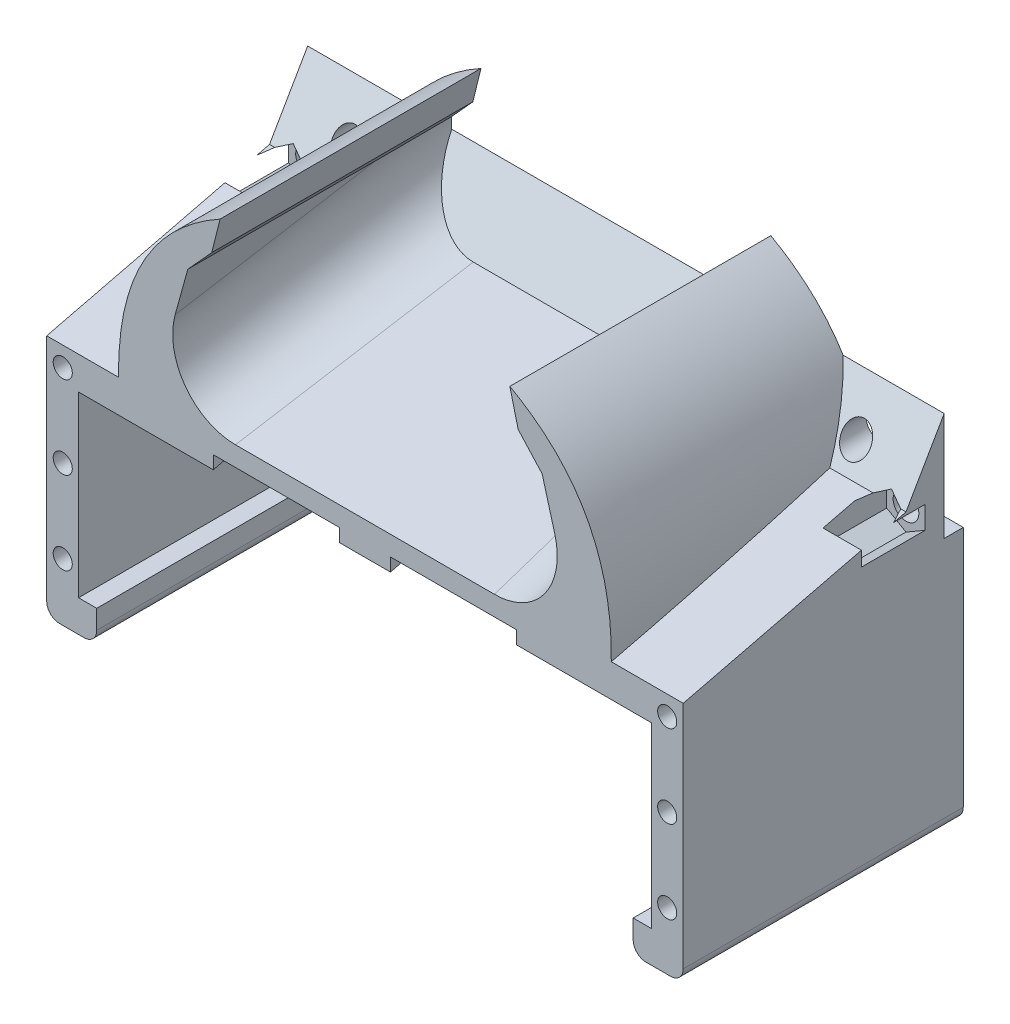
SolidWorks part; units mm, degrees
ref_plane "Alzado" through (0, 0, 0) normal (0, 0, 1) x (1, 0, 0)
ref_plane "Planta" through (0, 0, 0) normal (0, 1, 0) x (1, 0, 0)
ref_plane "Vista lateral" through (0, 0, 0) normal (1, 0, 0) x (0, 0, -1)
sketch "Croquis1" plane through (0, 0, 0) normal (0, 0, 1) x (1, 0, 0)
  line L0 (-50, -27.25) -> (-50, -29.8252)
  line L1 (-50, 27.25) -> (50, 27.25)
  line L2 (-50, 27.25) -> (-50, -27.25)
  line L4 (50, 27.25) -> (50, -27.25)
  line L5 (-50, 27.25) -> (50, -27.25) construction
  line L6 (-50, -27.25) -> (50, 27.25) construction
  line L8 (50, -29.8252) -> (50, -27.25)
  line L9 (50, -29.8252) -> (-50, -29.8252)
  point P0 (0, 0)
  dimension "D1" = 100
  dimension "D2" = 54.5
extrude "Saliente-Extruir1" add sketch "Croquis1" along normal blind 46
sketch "Croquis3" plane through (-50, 0, 0) normal (-1, 0, 0) x (0, 0, 1)
  line L0 (5, 27.25) -> (11, 16.8577)
  line L1 (46, 27.25) -> (0, 27.25) construction
  line L2 (5, 27.25) -> (5, 10.25)
  line L3 (0, 35.6144) -> (0, 11.6144) construction
  line L4 (5, 10.25) -> (-12.1741, 10.25)
  line L5 (-12.1741, 10.25) -> (-12.1741, 43.3906)
  line L6 (5, 27.25) -> (0.1443, 35.6603)
  line L7 (-12.1741, 43.3906) -> (41, 43.3906)
  line L9 (11, 16.8577) -> (46, 8.3186)
  line L10 (46, 27.25) -> (46, -29.8252) construction
  line M5 (0, 27.25) -> (0, -29.8252)
  line M7 (46, -29.8252) -> (46, 27.25)
  line M8 (46, 27.25) -> (0, 27.25)
  dimension "D2" = 17
  dimension "D1" = 5
  dimension "D3" = 12
  dimension "D4" = 30
extrude "Cortar-Extruir1" cut sketch "Croquis3" against normal blind 107 contours L0 M7 M8 | L7 L5 L4 M5 M8 region at (-50, 19.9452, 28.9845) region at (-50, 18.75, 2.5)
shell "Vaciado1" thickness 5 removed face at (0, -10.7533, 46)
sketch "Croquis5" plane through (0, 0, 0) normal (0, 0, -1) x (-1, 0, 0)
  line L0 (-44.969, -22.9415) -> (-44.969, -34.966)
  line L1 (-44.969, 22.9415) -> (44.969, 22.9415)
  line L2 (-44.969, 22.9415) -> (-44.969, -22.9415)
  line L4 (44.969, 22.9415) -> (44.969, -22.9415)
  line L5 (-44.969, 22.9415) -> (44.969, -22.9415) construction
  line L6 (-44.969, -22.9415) -> (44.969, 22.9415) construction
  line L7 (-44.969, -34.966) -> (44.969, -34.966)
  line L8 (44.969, -34.966) -> (44.969, -22.9415)
  point P0 (0, 0)
extrude "Cortar-Extruir3" cut sketch "Croquis5" against normal blind 5 contours L7 L8 L0 | L4 L1 L2 | L8 L0 region at (0, -6.0122, 0)
sketch "Croquis7" plane through (0, 0, 0) normal (0, 0, -1) x (-1, 0, 0)
  line L1 (-14.0425, 6.8203) -> (14.0425, 6.8203)
  line L2 (-14.0425, 6.8203) -> (-14.0425, -6.8203)
  line L3 (-14.0425, -6.8203) -> (14.0425, -6.8203)
  line L4 (14.0425, 6.8203) -> (14.0425, -6.8203)
  line L5 (-14.0425, 6.8203) -> (14.0425, -6.8203) construction
  line L6 (-14.0425, -6.8203) -> (14.0425, 6.8203) construction
  point P0 (0, 0)
extrude "Cortar-Extruir5" cut sketch "Croquis7" against normal blind 2 rebuild error yes
sketch "Croquis8" plane through (0, 0, 2) normal (0, 0, -1) x (-1, 0, 0)
  line L5 (-44.969, -42.8534) -> (44.969, -42.8534) construction
  line L11 (-42.1434, -13.3473) -> (42.1434, -13.3473)
  line L12 (-42.1434, -13.3473) -> (-42.1434, -72.3596)
  line L13 (-42.1434, -72.3596) -> (42.1434, -72.3596)
  line L14 (42.1434, -13.3473) -> (42.1434, -72.3596)
  line L15 (-42.1434, -13.3473) -> (42.1434, -72.3596) construction
  line L16 (-42.1434, -72.3596) -> (42.1434, -13.3473) construction
  point P0 (0, -42.8534)
  point P3 (0, -42.8534)
extrude "Cortar-Extruir6" cut sketch "Croquis8" against normal blind 50
sketch "Croquis9" plane through (0, 0, 5) normal (0, 0, -1) x (-1, 0, 0)
  line L0 (-44.969, 13.7411) -> (44.969, 13.7411)
  line L1 (44.969, 13.7411) -> (44.969, 5.25)
  line L2 (44.969, 5.25) -> (-44.969, 5.25)
  line L3 (-44.969, -29.8252) -> (-44.969, 10.25) construction
  line L4 (-44.969, 10.25) -> (-44.969, 5.25) construction
  line L5 (-44.969, 5.25) -> (-44.969, 13.7411)
extrude "Cortar-Extruir7" cut sketch "Croquis9" against normal blind 10
fillet "Redondeo1" radius 2 2 edges at (42.1434, -29.8252, 25.5) (-50, -29.8252, 23)
fillet "Redondeo2" radius 2 1 edges at (50, -29.8252, 23)
fillet "Redondeo3" radius 2 1 edges at (-42.1434, -29.8252, 25.5)
sketch "Croquis10" plane through (0, 13.5861, 3.3147) normal (0, -0.9715, -0.237) x (1, 0, 0)
  line L0 (23.8272, 1.7967) -> (23.8272, 43.9374)
  line L2 (45, 43.9374) -> (-45, 43.9374) construction
  line L3 (23.8272, 43.9374) -> (4, 43.9374)
  line L4 (4, 43.9374) -> (4, 1.7967)
  line L5 (4, 1.7967) -> (23.8272, 1.7967)
  line L6 (0, 0) -> (0, -11.1234) construction
  line L7 (-4, 1.7967) -> (-23.8272, 1.7967)
  line L8 (-4, 43.9374) -> (-4, 1.7967)
  line L9 (-23.8272, 43.9374) -> (-4, 43.9374)
  line L10 (-23.8272, 1.7967) -> (-23.8272, 43.9374)
  dimension "D1" = 4
extrude "Cortar-Extruir8" cut sketch "Croquis10" against normal blind 2
sketch "Croquis11" plane through (0, 0, 0) normal (0, 0, -1) x (-1, 0, 0)
  circle A0 centre (-47, 14.6144) radius 2.0175
  circle A1 centre (47, 14.6144) radius 1.8911
extrude "Cortar-Extruir9" cut sketch "Croquis11" against normal blind 9
sketch "Croquis12" plane through (0, 0, 0) normal (0, 0, -1) x (-1, 0, 0)
  circle A0 centre (40, 20.6144) radius 2.25
  circle A1 centre (-40, 20.6144) radius 2.25
extrude "Cortar-Extruir10" cut sketch "Croquis12" against normal blind 33
sketch "Croquis13" plane through (0, 0, 5) normal (0, 0, -1) x (-1, 0, 0)
  line L0 (0, 0) -> (0, -9.6191) construction
  line L7 (-14.0425, -6.8203) -> (14.0425, 6.8203) construction
  circle A0 centre (47, 14.6144) radius 2.075
  circle A1 centre (-47, 14.6144) radius 2.075
  dimension "D1" = 4.15
extrude "Cortar-Extruir11" cut sketch "Croquis13" against normal blind 7 from offset 3 offset against normal yes
sketch "Croquis14" plane through (0, 0, 5) normal (0, 0, -1) x (-1, 0, 0)
  line L0 (0, 0) -> (0, -3.5033) construction
  circle A1 centre (-47, 14.6144) radius 2.5
  circle A2 centre (47, 14.6144) radius 2.5
  dimension "D1" = 5
extrude "Cortar-Extruir12" cut sketch "Croquis14" along normal blind 20 and the other way blind 1 from offset 10 rebuild error yes offset against normal yes
sketch "Croquis15" plane through (0, 0, 15) normal (0, 0, -1) x (-1, 0, 0)
  line L0 (-44.969, 10.7351) -> (-37.0015, 10.7351)
  line L1 (-44.969, 10.7351) -> (-23.8272, 10.7351) construction
  line L2 (-37.0015, 10.7351) -> (-37.0015, 13.7411)
  line L3 (44.969, 13.7411) -> (-44.969, 13.7411) construction
  line L4 (-44.969, 10.7351) -> (-44.969, 13.7411)
  line L5 (-44.969, 13.7411) -> (-37.0015, 13.7411)
  line L6 (0, 0) -> (0, 2.3673)
  line L7 (44.969, 13.7411) -> (37.0015, 13.7411)
  line L8 (44.969, 10.7351) -> (44.969, 13.7411)
  line L9 (37.0015, 10.7351) -> (37.0015, 13.7411)
  line L10 (44.969, 10.7351) -> (37.0015, 10.7351)
  line M3 (-44.969, 13.7411) -> (-44.969, 10.7351)
  line M4 (-44.969, 10.7351) -> (-23.8272, 10.7351)
  line M12 (23.8272, 10.7351) -> (44.969, 10.7351)
  line M13 (44.969, 10.7351) -> (44.969, 13.7411)
  line M15 (44.969, 13.7411) -> (-44.969, 13.7411)
extrude "Saliente-Extruir2" add sketch "Croquis15" along normal blind 10 contours L2 M4 M15 M3 | L9 M12 M13 M15 region at (40.9852, 12.2381, 15) region at (-40.9852, 12.2381, 15)
sketch "Croquis16" plane through (0, 0, 0) normal (0, 0, -1) x (-1, 0, 0)
  line L0 (-44.969, 10.25) -> (-50, 10.25) construction
  line L1 (0, 0) -> (0, -14.3372) construction
  circle A0 centre (-47.4845, 5.25) radius 1.5
  circle A1 centre (-47.4845, -20.75) radius 1.5
  circle A2 centre (-47.4845, -7.75) radius 1.5
  circle A3 centre (47.4845, -7.75) radius 1.5
  circle A4 centre (47.4845, -20.75) radius 1.5
  circle A5 centre (47.4845, 5.25) radius 1.5
  point P8 (-47.4845, 10.25)
  dimension "D1" = 3
  dimension "D2" = 3
  dimension "D3" = 3
  dimension "D4" = 13
  dimension "D5" = 13
  dimension "D6" = 5
extrude "Cortar-Extruir13" cut sketch "Croquis16" against normal blind 73
sketch "Croquis17" plane through (0, 0, 0) normal (0, 0, -1) x (-1, 0, 0)
  line L1 (-62.0795, 36.9151) -> (62.0795, 36.9151)
  line L2 (-62.0795, 36.9151) -> (-62.0795, -36.9151)
  line L3 (-62.0795, -36.9151) -> (62.0795, -36.9151)
  line L4 (62.0795, 36.9151) -> (62.0795, -36.9151)
  line L5 (-62.0795, 36.9151) -> (62.0795, -36.9151) construction
  line L6 (-62.0795, -36.9151) -> (62.0795, 36.9151) construction
  point P0 (0, 0)
extrude "Cortar-Extruir14" cut sketch "Croquis17" against normal blind 2
sketch "Croquis18" plane through (0, 0, 46) normal (0, 0, 1) x (1, 0, 0)
  line L0 (-50, 8.3186) -> (50, 8.3186)
  line L1 (50, 8.3186) -> (50, 5.461)
  line L2 (50, -27.8252) -> (50, 8.3186) construction
  line L3 (50, 5.461) -> (-50, 5.461)
  line L4 (-50, 8.3186) -> (-50, -27.8252) construction
  line L5 (-50, 5.461) -> (-50, 8.3186)
sketch "Croquis19" plane through (0, 0, 8) normal (0, 0, 1) x (1, 0, 0)
  line L0 (0, 0) -> (0, -17.6249) construction
  line L1 (47, 11.1144) -> (50.0311, 12.8644)
  line L2 (50.0311, 12.8644) -> (50.0311, 16.3644)
  line L3 (50.0311, 16.3644) -> (47, 18.1144)
  line L4 (47, 18.1144) -> (43.9689, 16.3644)
  line L5 (43.9689, 16.3644) -> (43.9689, 12.8644)
  line L6 (43.9689, 12.8644) -> (47, 11.1144)
  line L7 (-43.9689, 12.8644) -> (-47, 11.1144)
  line L8 (-43.9689, 16.3644) -> (-43.9689, 12.8644)
  line L9 (-47, 18.1144) -> (-43.9689, 16.3644)
  line L10 (-50.0311, 16.3644) -> (-47, 18.1144)
  line L11 (-50.0311, 12.8644) -> (-50.0311, 16.3644)
  line L12 (-47, 11.1144) -> (-50.0311, 12.8644)
  circle A0 centre (47, 14.6144) radius 3.0311 construction
  circle A1 centre (-47, 14.6144) radius 3.0311 construction
  dimension "D1" = 7
extrude "Cortar-Extruir15" cut sketch "Croquis19" along normal blind 10
sketch "Croquis21" plane through (0, 0, 46) normal (0, 0, 1) x (1, 0, 0)
  line L0 (-50, 8.3186) -> (50, 8.3186) construction
  line L1 (-22.7634, 37.8244) -> (-24.0671, 32.6096)
  line L2 (-24.0671, 32.6096) -> (-27.8333, 28.4632)
  line L3 (-27.8333, 28.4632) -> (-33.4148, 8.3186)
  line L4 (0, 0) -> (0, -17.8009) construction
  line L5 (14.0425, -6.8203) -> (-14.0425, 6.8203) construction
  line L6 (27.8333, 28.4632) -> (33.4148, 8.3186)
  line L7 (24.0671, 32.6096) -> (27.8333, 28.4632)
  line L8 (22.7634, 37.8244) -> (24.0671, 32.6096)
  line L9 (-38.6973, 8.3186) -> (-33.4148, 8.3186)
  line L10 (33.4148, 8.3186) -> (38.6973, 8.3186)
  spline S0 degree 2 poles (-38.6973, 8.3186) (-39.0508, 28.7688) (-22.7634, 37.8244) knots 0 0 0 1 1 1
  spline S1 degree 2 poles (38.6973, 8.3186) (39.0508, 28.7688) (22.7634, 37.8244) knots 0 0 0 1 1 1
extrude "Saliente-Extruir3" add sketch "Croquis21" against normal blind 41
sketch "Croquis23" plane through (0, 0, 46) normal (0, 0, 1) x (1, 0, 0)
  line L0 (28.1694, 27.25) -> (-28.1694, 27.25) construction
  circle A0 centre (0, 27.25) radius 12.5
  dimension "D1" = 25
fillet "Redondeo4" radius 10 2 edges at (-32.2318, 12.5881, 28.5) (32.2318, 12.5881, 28.5)
